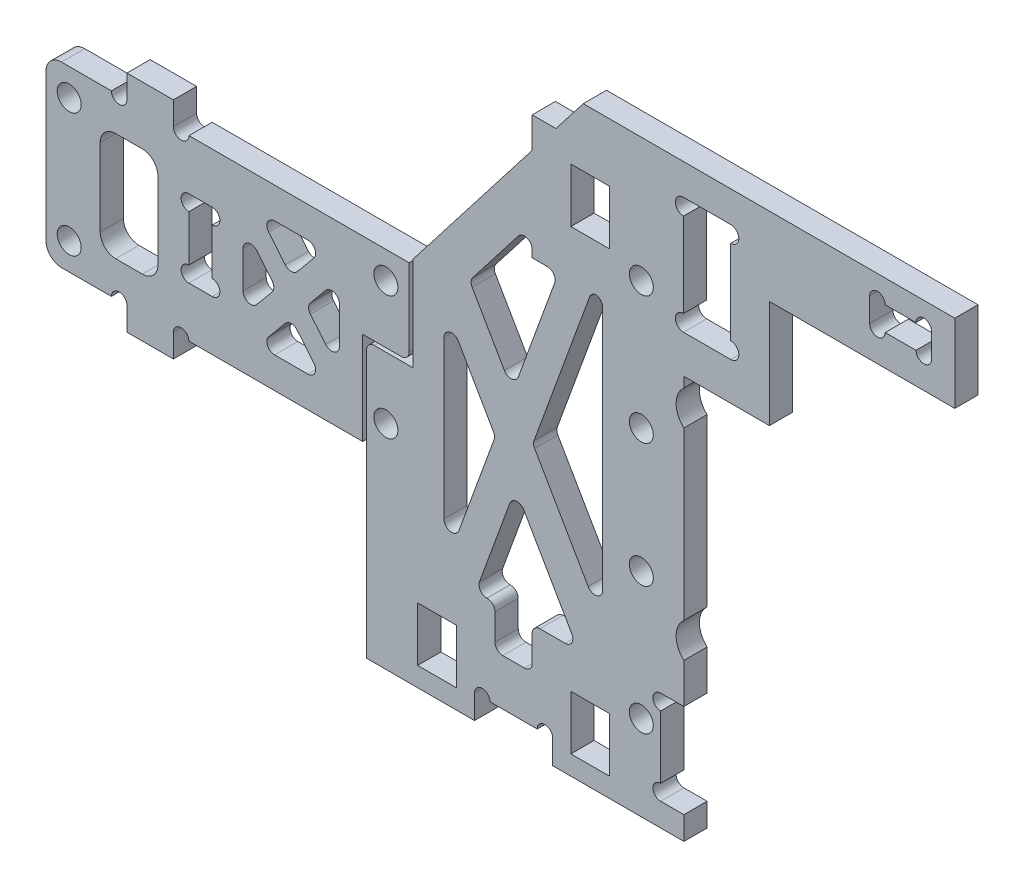
SolidWorks part; units mm, degrees
material "Thornel Mat VMA"
ref_plane "前视基准面" through (0, 0, 0) normal (0, 0, 1) x (1, 0, 0)
ref_plane "上视基准面" through (0, 0, 0) normal (0, 1, 0) x (1, 0, 0)
ref_plane "右视基准面" through (0, 0, 0) normal (1, 0, 0) x (0, 0, -1)
sketch "草图1" plane through (0, 0, 0) normal (0, 0, 1) x (1, 0, 0)
  line L0 (-13, 11.5) -> (-13, 14.5)
  line L1 (23.455, -11.5) -> (17.955, -11.5) construction
  line L2 (23.455, -11.5) -> (23.455, 11.5) construction
  line L3 (23.455, 11.5) -> (-7, 11.5)
  line L4 (-23.455, -11.5) -> (-23.455, 11.5)
  line L5 (23.455, -11.5) -> (-23.455, 11.5) construction
  line L6 (23.455, 11.5) -> (-23.455, -11.5) construction
  line L7 (-20.455, 8) -> (-20.455, -8) construction
  line L8 (-20.455, 0) -> (0, 0) construction
  line L9 (0, 0) -> (0, 8.6559) construction
  line L10 (-2, -5) -> (-5, -5)
  line L11 (-2, -5) -> (-2, 5)
  line L12 (-2, 5) -> (-5, 5)
  line L13 (-5, -5) -> (-5, 5)
  line L14 (-2, -5) -> (-5, 5) construction
  line L15 (-2, 5) -> (-5, -5) construction
  line L16 (-13, 14.5) -> (-7, 14.5)
  line L17 (-7, 14.5) -> (-7, 11.5)
  line L18 (-13, 11.5) -> (-23.455, 11.5)
  line L19 (-7, -14.5) -> (-7, -11.5)
  line L20 (-13, -14.5) -> (-7, -14.5)
  line L21 (-13, -11.5) -> (-13, -14.5)
  line L22 (-13, -11.5) -> (-23.455, -11.5)
  line L23 (12.5053, -7.5) -> (8.2275, -2.3481)
  line L28 (-9, 7) -> (-16.455, 7)
  line L29 (-9, 7) -> (-9, -7)
  line L30 (12.5053, 7.5) -> (3.9497, 7.5)
  line L31 (14.455, 5.1519) -> (14.455, -5.1519)
  line L32 (12.5053, -7.5) -> (3.9497, -7.5)
  line L33 (2, 5.1519) -> (2, -5.1519)
  line L34 (14.455, 7.5) -> (2, -7.5) construction
  line L35 (14.455, -7.5) -> (2, 7.5) construction
  line L36 (-9, -7) -> (-16.455, -7)
  line L37 (-16.455, 7) -> (-16.455, -7)
  line L38 (-9, 7) -> (-16.455, -7) construction
  line L39 (-9, -7) -> (-16.455, 7) construction
  line L40 (14.455, -5.1519) -> (10.1772, 0)
  line L41 (2, -5.1519) -> (6.2778, 0)
  line L42 (3.9497, -7.5) -> (8.2275, -2.3481)
  line L43 (6.2778, 0) -> (2, 5.1519)
  line L44 (8.2275, 2.3481) -> (3.9497, 7.5)
  line L45 (10.1772, 0) -> (14.455, 5.1519)
  line L46 (8.2275, 2.3481) -> (12.5053, 7.5)
  line L47 (23.455, -11.5) -> (23.455, -35.5) construction
  line L48 (23.455, -35.5) -> (31.9066, -35.5)
  line L49 (55.955, -35.5) -> (55.955, 13.9884)
  line L50 (93.955, 40.55) -> (45.955, 40.55)
  line L58 (42.0066, -35.5) -> (55.955, -35.5)
  line L59 (36.9566, -32.4) -> (36.9566, -35.5) construction
  line L60 (10.3106, -15) -> (21.6899, -15) construction
  line L64 (23.955, 12.1456) -> (45.955, 40.55)
  line L68 (17.455, -11.5) -> (-7, -11.5)
  line L69 (23.455, -11.5) -> (17.955, -11.5) construction
  line L70 (55.955, 16.55) -> (70.005, 16.55)
  line L71 (70.005, 16.55) -> (70.005, 30.45)
  line L74 (65.005, 36.55) -> (58.905, 36.55)
  line L75 (65.005, 36.55) -> (65.005, 21.45)
  line L76 (65.005, 21.45) -> (58.905, 21.45)
  line L77 (58.905, 36.55) -> (58.905, 21.45)
  line L78 (65.005, 36.55) -> (58.905, 21.45) construction
  line L79 (65.005, 21.45) -> (58.905, 36.55) construction
  line L80 (55.955, 13.9884) -> (55.955, 16.55)
  line L81 (70.005, 30.45) -> (93.955, 30.45)
  line L82 (93.955, 30.45) -> (93.955, 40.55)
  line L84 (23.455, -11.5) -> (23.455, -35.5) construction
  line L85 (90.955, 37.55) -> (82.955, 37.55)
  line L86 (90.955, 37.55) -> (90.955, 34.45)
  line L87 (90.955, 34.45) -> (82.955, 34.45)
  line L88 (82.955, 37.55) -> (82.955, 34.45)
  line L89 (90.955, 37.55) -> (82.955, 34.45) construction
  line L90 (90.955, 34.45) -> (82.955, 37.55) construction
  line L91 (23.455, -35.5) -> (17.955, -35.5)
  line L92 (17.955, -11.5) -> (17.955, -35.5)
  line L93 (17.955, -11.5) -> (17.955, 0)
  line L94 (17.955, 0) -> (23.955, 0)
  line L95 (23.955, 0) -> (23.955, 12.1456)
  line L96 (23.455, 11.5) -> (23.455, 0.5)
  line L97 (23.455, 0.5) -> (17.455, 0.5)
  line L98 (17.455, 0.5) -> (17.455, -11.5)
  line L99 (31.9066, -35.5) -> (31.9066, -32.4)
  line L100 (42.0066, -32.4) -> (31.9066, -32.4)
  line L101 (42.0066, -35.5) -> (42.0066, -32.4)
  line L103 (27.955, -26.4) -> (27.955, 9.1446) construction
  line L104 (27.955, 9.1446) -> (48.455, 35.6124) construction
  line L105 (48.455, 35.6124) -> (48.455, -26.4) construction
  line L106 (48.455, -26.4) -> (27.955, -26.4) construction
  line L107 (48.455, -26.4) -> (37.2032, -6.8907)
  line L108 (48.455, -16.3921) -> (39.4399, -0.761)
  line L109 (48.455, 23.9438) -> (39.4399, -0.761)
  line L110 (27.955, -20.5657) -> (34.5952, -2.3688)
  line L111 (27.955, -20.5657) -> (27.955, 9.1446)
  line L112 (31.2634, 13.4161) -> (48.455, 35.6124)
  line L113 (30.084, -26.4) -> (48.455, -26.4)
  line L114 (48.455, -16.3921) -> (48.455, 23.9438)
  line L115 (34.5952, -2.3688) -> (27.955, 9.1446)
  line L116 (36.832, 3.7608) -> (48.455, 35.6124)
  line L117 (36.832, 3.7608) -> (31.2634, 13.4161)
  line L118 (37.2032, -6.8907) -> (30.084, -26.4)
  circle A0 centre (-20.455, 8) radius 1.55
  circle A1 centre (-20.455, -8) radius 1.55
  circle A4 centre (20.455, -8) radius 1.55
  circle A5 centre (20.455, 8) radius 1.55
  circle A6 centre (-2, 3.995) radius 1.005
  circle A7 centre (-5, 3.995) radius 1.005
  circle A8 centre (-5, -3.995) radius 1.005
  circle A9 centre (-2, -3.995) radius 1.005
  circle A10 centre (-5.995, 11.5) radius 1.005
  circle A11 centre (-14.005, 11.5) radius 1.005
  circle A12 centre (-5.995, -11.5) radius 1.005
  circle A13 centre (-14.005, -11.5) radius 1.005
  circle A14 centre (53.455, -24.5) radius 1.55
  circle A15 centre (53.455, -8) radius 1.55
  circle A16 centre (53.455, 24.5) radius 1.55
  circle A17 centre (53.455, 8) radius 1.55
  circle A26 centre (65.005, 22.5) radius 1.05
  circle A27 centre (65.005, 35.5) radius 1.05
  circle A28 centre (58.905, 35.5) radius 1.05
  circle A29 centre (58.905, 22.5) radius 1.05
  circle A32 centre (83.96, 37.55) radius 1.005
  circle A33 centre (89.95, 37.55) radius 1.005
  circle A34 centre (89.95, 34.45) radius 1.005
  circle A35 centre (83.96, 34.45) radius 1.005
  point P0 (0, 0)
  point P7 (-3.5, 0)
  point P46 (-12.7275, 0)
  point P51 (8.2275, 0)
  point P119 (61.955, 29)
  point P135 (86.955, 36)
  dimension "D1" = 3.1
  dimension "D9" = 2.01
  dimension "D30" = 2.1
  dimension "D32" = 3.1
  dimension "D33" = 24
  dimension "D51" = 2.01
  dimension "D36" = 0.5
  dimension "D31" = 10
  dimension "D2" = 16
  dimension "D3" = 23
  dimension "D4" = 3
  dimension "D5" = 3
  dimension "D6" = 2
  dimension "D7" = 10
  dimension "D8" = 40.91
  dimension "D10" = 6
  dimension "D11" = 2
  dimension "D12" = 3
  dimension "D13" = 4
  dimension "D14" = 4.5
  dimension "D15" = 4
  dimension "D16" = 0.5
  dimension "D17" = 4
  dimension "D18" = 1.5
  dimension "D19" = 3
  dimension "D20" = 1.5
  dimension "D21" = 3
  dimension "D22" = 16
  dimension "D23" = 49
  dimension "D24" = 33
  dimension "D25" = 4
  dimension "D26" = 15
  dimension "D27" = 3.1
  dimension "D28" = 10.1
  dimension "D29" = 18.9984
  dimension "D34" = 2.5
  dimension "D35" = 4
  dimension "D37" = 2.5
  dimension "D38" = 5
  dimension "D39" = 6.1
  dimension "D40" = 15.1
  dimension "D41" = 6
  dimension "D42" = 0.5
  dimension "D43" = 29
  dimension "D44" = 4.9
  dimension "D45" = 3.1
  dimension "D46" = 8
  dimension "D47" = 25
  dimension "D48" = 7
  dimension "D49" = 4
  dimension "D50" = 3
  dimension "D52" = 3
  dimension "D53" = 6
  dimension "D54" = 4
  dimension "D55" = 5
  dimension "D56" = 5
  dimension "D57" = 5
  dimension "D58" = 2
  dimension "D59" = 4
extrude "凸台-拉伸1" add sketch "草图1" along normal blind 3 contours A11 L18 L4 L1 L2 L3 A10 L17 L16 L0 A9 L10 A8 L13 A7 L12 A6 L11 A4 A1 A0 A5 | L101 L58 L49 L80 L70 L71 L81 L82 L50 L64 L95 L94 L93 L92 L91 L48 L99 L100 A35 L88 A32 L85 A33 L86 A34 L87 A29 L77 A28 L74 A27 L75 A26 L76 A16 A15 A14 A4 A17 region at (-1.1268, 0.4275, 0) region at (20.705, -34.4248, 0)
fillet "圆角1" radius 2 6 edges at (-23.455, 11.5, 1.5) (-23.455, -11.5, 1.5) (-16.455, 7, 1.5) (-9, 7, 1.5) (-9, -7, 1.5) (-16.455, -7, 1.5)
fillet "圆角2" radius 1 12 edges at (12.5053, 7.5, 1.5) (3.9497, 7.5, 1.5) (8.2275, 2.3481, 1.5) (2, 5.1519, 1.5) (2, -5.1519, 1.5) (6.2778, 0, 1.5) (12.5053, -7.5, 1.5) (8.2275, -2.3481, 1.5) (14.455, -5.1519, 1.5) (14.455, 5.1519, 1.5) (10.1772, 0, 1.5) (3.9497, -7.5, 1.5)
sketch "草图5" plane through (0, 0, 3) normal (0, 0, 1) x (1, 0, 0)
  line L1 (55.955, -35.5) -> (58.955, -35.5)
  line L2 (55.955, -35.5) -> (55.955, -32.5)
  line L3 (55.955, -32.5) -> (58.955, -32.5)
  line L4 (58.955, -35.5) -> (58.955, -32.5)
  line L5 (57.455, -32.5) -> (57.455, -35.5) construction
  line L6 (55.955, -34) -> (58.955, -34) construction
  line L7 (55.955, -20.4) -> (58.955, -20.4)
  line L8 (55.955, -20.4) -> (55.955, -5.5)
  line L9 (55.955, -5.5) -> (58.955, -5.5) construction
  line L10 (58.955, -20.4) -> (58.955, -5.5)
  line L11 (57.455, -5.5) -> (57.455, -20.4) construction
  line L12 (55.955, -12.95) -> (58.955, -12.95) construction
  line L19 (55.955, 5.6) -> (58.955, 5.6) construction
  line L20 (55.955, 5.6) -> (55.955, 16.55)
  line L21 (55.955, 16.55) -> (58.955, 16.55)
  line L22 (58.955, 5.6) -> (58.955, 16.55)
  line L23 (57.455, 16.55) -> (57.455, 5.6) construction
  line L24 (55.955, 11.075) -> (58.955, 11.075) construction
  line L26 (55.955, -5.5) -> (55.955, 5.6)
  line L27 (58.955, -5.5) -> (58.955, 5.6)
  line L28 (55.955, -35.5) -> (55.955, 16.55) construction
  line L29 (42.0066, -35.5) -> (55.955, -35.5) construction
  line L30 (55.955, 16.55) -> (70.005, 16.55) construction
  point P96 (57.455, -34)
  point P180 (57.455, 11.075)
  point P358 (57.455, -12.95)
  dimension "D1" = 3
  dimension "D2" = 3
  dimension "D3" = 12.1
  dimension "D4" = 14.9
  dimension "D5" = 11.1
extrude "凸台-拉伸2" add sketch "草图5" against normal up to surface (3 mm away) up to face at (-3.5, 0, 0)
sketch "草图4" plane through (0, 0, 3) normal (0, 0, 1) x (1, 0, 0)
  line L0 (36.955, -35.1451) -> (36.955, -22.7276) construction
  line L1 (49.355, -26) -> (44.355, -26)
  line L2 (49.355, -26) -> (49.355, -33)
  line L3 (49.355, -33) -> (44.355, -33)
  line L4 (44.355, -26) -> (44.355, -33)
  line L5 (46.855, -33) -> (46.855, -26) construction
  line L6 (49.355, -29.5) -> (44.355, -29.5) construction
  line L8 (24.555, -33) -> (29.555, -33)
  line L9 (29.555, -26) -> (29.555, -33)
  line L10 (24.555, -26) -> (29.555, -26)
  line L11 (24.555, -26) -> (24.555, -33)
  line L13 (55.955, 0) -> (-23.455, 0) construction
  line L14 (-23.455, -9.5) -> (-23.455, 9.5) construction
  line L15 (49.355, 33) -> (44.355, 33)
  line L16 (44.355, 26) -> (44.355, 33)
  line L17 (49.355, 26) -> (44.355, 26)
  line L18 (49.355, 26) -> (49.355, 33)
  line L19 (24.555, 26) -> (24.555, 33)
  line L20 (24.555, 26) -> (29.555, 26)
  line L21 (29.555, 26) -> (29.555, 33)
  line L22 (24.555, 33) -> (29.555, 33)
  line L23 (27.055, -33) -> (27.055, -26) construction
  line L25 (55.955, -32.5) -> (55.955, -20.4) construction
  line L48 (31.9066, -35.5) -> (17.955, -35.5) construction
  line L49 (58.955, -32.5) -> (55.955, -32.5) construction
  line L51 (55.955, -20.4) -> (58.955, -20.4) construction
  line L52 (42.0066, -32.4) -> (31.9066, -32.4) construction
  line L53 (31.9066, -35.5) -> (31.9066, -32.4) construction
  line L54 (42.0066, -35.5) -> (42.0066, -32.4) construction
  circle A0 centre (55.955, -21.4) radius 1
  circle A3 centre (55.955, -31.5) radius 1
  circle A6 centre (41.0066, -32.4) radius 1
  circle A7 centre (32.9066, -32.4) radius 1
  point P120 (46.855, -29.5)
  dimension "D7" = 2
  dimension "D8" = 2
  dimension "D1" = 9.1
  dimension "D2" = 6
  dimension "D3" = 19.8
  dimension "D4" = 5
  dimension "D5" = 7
  dimension "D6" = 59
extrude "切除-拉伸2" cut sketch "草图4" against normal through all
fillet "圆角3" radius 1 1 edges at (17.955, 0, 1.5)
fillet "圆角4" radius 1 1 edges at (23.455, 0.5, 1.5)
sketch "草图6" plane through (0, 0, 3) normal (0, 0, 1) x (1, 0, 0)
  line L0 (29.555, -30.4) -> (29.555, -26)
  line L1 (29.555, -26) -> (24.555, -26)
  line L2 (24.555, -26) -> (24.555, -21)
  line L3 (24.555, -21) -> (34.555, -21)
  line L4 (34.555, -21) -> (34.555, -30.4)
  line L5 (34.555, -30.4) -> (29.555, -30.4)
  line L6 (44.355, -26.4) -> (44.355, -26)
  line L7 (44.355, -26) -> (49.355, -26)
  line L8 (49.355, -26) -> (49.355, -21)
  line L9 (49.355, -21) -> (39.355, -21)
  line L10 (39.355, -21) -> (39.355, -30.4)
  line L11 (39.355, -30.4) -> (44.355, -30.4)
  line L12 (29.555, -33) -> (29.555, -26) construction
  line L13 (44.355, -30.4) -> (44.355, -26.4)
  line L14 (49.355, 26) -> (49.355, 33)
  line L15 (49.355, 33) -> (44.355, 33)
  line L16 (44.355, 33) -> (44.355, 26)
  line L17 (44.355, 26) -> (49.355, 26)
  line L18 (39.355, 36) -> (39.355, 20)
  line L19 (39.355, 20) -> (50.355, 20)
  line L20 (50.355, 20) -> (50.355, 36)
  line L21 (50.355, 36) -> (39.355, 36)
  line L22 (40.0066, -32.4) -> (33.9066, -32.4) construction
  dimension "D1" = 2
  dimension "D2" = 5
  dimension "D3" = 5
  dimension "D4" = 5
  dimension "D5" = 5
  dimension "D6" = 5
  dimension "D7" = 3
  dimension "D8" = 1
  dimension "D9" = 6
extrude "凸台-拉伸3" add sketch "草图6" along direction (0, 0, 1) on the side against the normal up to surface (3 mm away) up to face at (27.055, -29.5, 0)
fillet "圆角5" radius 1 18 edges at (31.2634, 13.4161, 1.5) (42.7579, 20, 1.5) (36.832, 3.7608, 1.5) (39.4399, -0.761, 1.5) (48.455, 20, 1.5) (47.0159, 20, 1.5) (48.455, -16.3921, 1.5) (39.355, -21, 1.5) (39.355, -26.4, 1.5) (34.555, -26.4, 1.5) (32.0545, -21, 1.5) (37.2032, -6.8907, 1.5) (45.3406, -21, 1.5) (34.555, -21, 1.5) (27.955, 9.1446, 1.5) (34.5952, -2.3688, 1.5) (27.955, -20.5657, 1.5) (39.355, 23.8632, 1.5)
sketch "草图7" plane through (0, 0, 3) normal (0, 0, 1) x (1, 0, 0)
  line L0 (47.1045, 0) -> (61.7652, 0) construction
  line L2 (58.955, -20.4) -> (58.955, 16.55) construction
  circle A0 centre (53.455, -8) radius 1.55 construction
  circle A1 centre (53.455, 8) radius 1.55 construction
  circle A2 centre (60.955, -13) radius 3
  circle A3 centre (60.955, 13) radius 3
  point P8 (63.3669, -13)
  point P12 (58.955, -5.7769)
  point P13 (0, 0)
  point P14 (58.955, -7.0208)
  point P15 (0, 0)
  point P16 (0, 0)
  dimension "D1" = 6
  dimension "D2" = 26
  dimension "D3" = 2
extrude "切除-拉伸3" cut sketch "草图7" against normal blind 10
